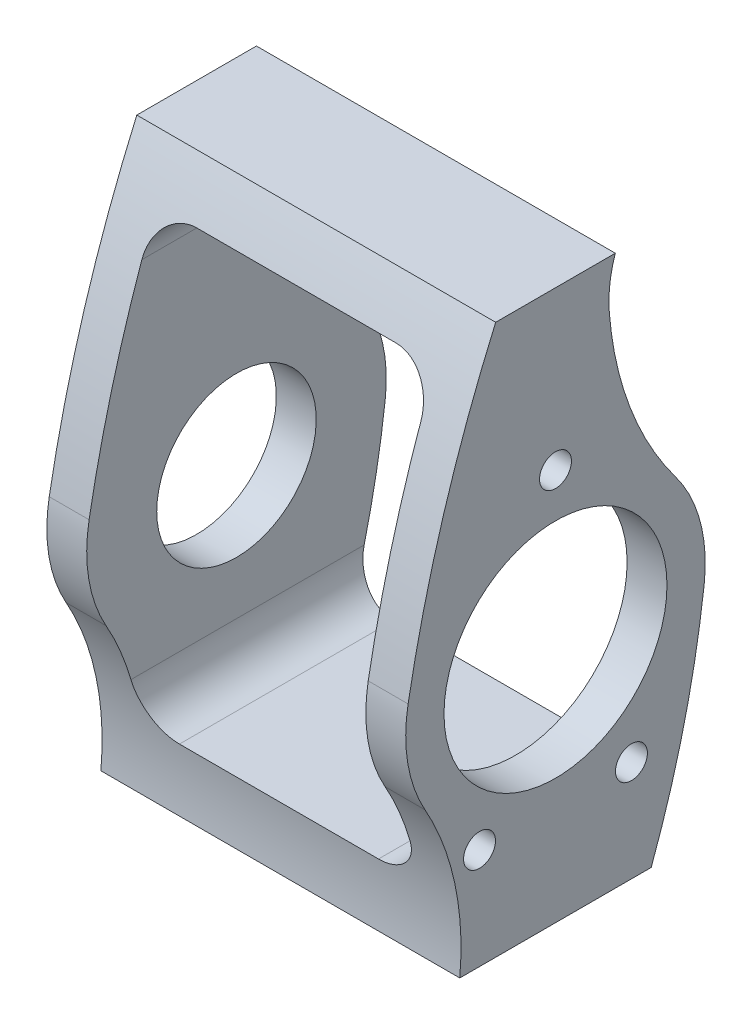
SolidWorks part; units mm, degrees
material "AISI 4340 Steel, normalized"
ref_plane "Front Plane" through (0, 0, 0) normal (0, 0, 1) x (1, 0, 0)
ref_plane "Top Plane" through (0, 0, 0) normal (0, 1, 0) x (1, 0, 0)
ref_plane "Right Plane" through (0, 0, 0) normal (1, 0, 0) x (0, 0, -1)
other "Center of Mass"
sketch "Sketch1" plane through (0, 0, 0) normal (1, 0, 0) x (0, 0, -1)
  line L0 (9.525, 49.899) -> (-9.525, 49.899)
  line L1 (9.525, 49.899) -> (-7.4687, 0) construction
  line L2 (0, 0) -> (9.525, 49.899) construction
  line L3 (-15.24, -37.6743) -> (15.24, -37.6743)
  line L4 (-15.24, -37.6743) -> (0, 0) construction
  line L5 (0, 0) -> (0, -50.8) construction
  line L6 (-7.3617, -24.2335) -> (-7.431, -18.808) construction
  line L7 (-7.431, -18.808) -> (-12.1642, -16.1553) construction
  line L8 (-12.1642, -16.1553) -> (-16.8282, -18.928) construction
  line L9 (-16.8282, -18.928) -> (-16.7589, -24.3535) construction
  line L10 (-16.7589, -24.3535) -> (-12.0257, -27.0063) construction
  line L11 (-12.0257, -27.0063) -> (-7.3617, -24.2335) construction
  line L12 (16.7589, -24.3535) -> (16.8282, -18.928) construction
  line L13 (16.8282, -18.928) -> (12.1642, -16.1553) construction
  line L14 (12.1642, -16.1553) -> (7.431, -18.808) construction
  line L15 (7.431, -18.808) -> (7.3617, -24.2335) construction
  line L16 (7.3617, -24.2335) -> (12.0257, -27.0063) construction
  line L17 (12.0257, -27.0063) -> (16.7589, -24.3535) construction
  line L18 (2.713, 20.04) -> (5.4259, 24.739) construction
  line L19 (5.4259, 24.739) -> (2.713, 29.438) construction
  line L20 (2.713, 29.438) -> (-2.713, 29.438) construction
  line L21 (-2.713, 29.438) -> (-5.4259, 24.739) construction
  line L22 (-5.4259, 24.739) -> (-2.713, 20.04) construction
  line L23 (-2.713, 20.04) -> (2.713, 20.04) construction
  line L24 (-15.4577, -27.5143) -> (18.4762, -27.5143) construction
  line L25 (15.24, -37.6743) -> (15.24, -27.5143) construction
  line L26 (12.0949, -21.5808) -> (-12.0949, -21.5808) construction
  circle A0 centre (0, 0) radius 17.5 construction
  circle A1 centre (0, 0) radius 20.04 construction
  circle A2 centre (0, 0) radius 50.8 construction
  circle A3 centre (0, 0) radius 40.64 construction
  circle A4 centre (0, 0) radius 23.85 construction
  circle A7 centre (-12.0949, -21.5808) radius 4.699 construction
  circle A8 centre (12.0949, -21.5808) radius 4.699 construction
  circle A9 centre (0, 24.739) radius 4.699 construction
  arc A12 (9.525, 49.899) -> (8.5654, 42.279) centre (27.5579, 43.7577) ccw
  arc A13 (19.0999, 14.2834) -> (8.5654, 42.279) centre (62.1106, 46.4478) cw
  arc A14 (-15.24, -37.6743) -> (-20.7762, -11.7121) centre (-59.4974, -33.5404) ccw
  arc A15 (-20.7762, -11.7121) -> (-23.4703, 4.2386) centre (0, 0) cw
  arc A16 (23.6786, -2.8538) -> (19.0999, 14.2834) centre (0, 0) ccw
  arc A18 (-9.525, 49.899) -> (-23.4703, 4.2386) centre (176.495, -31.8738) ccw
  arc A19 (15.24, -37.6743) -> (23.6786, -2.8538) centre (-127.6264, 15.3818) ccw
  point P37 (9.7976, -17.4817)
  point P38 (-9.7976, -17.4817)
  point P39 (0, 20.04)
  point P56 (0, -21.5808)
  dimension "D1" = 35
  dimension "D3" = 101.6
  dimension "D13" = 19.05
  dimension "D15" = 44.45
  dimension "D16" = 152.4
  dimension "D17" = 203.2
  dimension "D2" = 2.54
  dimension "D4" = 10.16
  dimension "D5" = 8
  dimension "D7" = 6.35
  dimension "D8" = 9.398
  dimension "D6" = 19.05
  dimension "D9" = 90
  dimension "D10" = 10.16
  dimension "D11" = 0.508
  dimension "D12" = 30.48
  dimension "D14" = 7.62
extrude "Boss-Extrude1" add sketch "Sketch1" along normal blind 57.15
sketch "Sketch2" plane through (0, 0, 0) normal (0, 0, 1) x (1, 0, 0)
  line L0 (57.15, 49.899) -> (0, 49.899) construction
  line L1 (6.35, 42.279) -> (50.8, 42.279)
  line L2 (6.35, 42.279) -> (6.35, -27.5143)
  line L3 (6.35, -27.5143) -> (50.8, -27.5143)
  line L4 (50.8, 42.279) -> (50.8, -27.5143)
  line L5 (57.15, -37.6743) -> (0, -37.6743) construction
  line L6 (0, 49.899) -> (0, 4.2386) construction
  line L7 (57.15, 4.2386) -> (57.15, 49.899) construction
  dimension "D1" = 7.62
  dimension "D2" = 10.16
  dimension "D3" = 6.35
  dimension "D4" = 6.35
extrude "Cut-Extrude1" cut sketch "Sketch2" against normal through all both and the other way through all
fillet "Fillet1" radius 6.3754 4 edges at (6.35, -27.5143, -1.5772) (6.35, 42.279, 2.0631) (50.8, 42.279, 2.0631) (50.8, -27.5143, -1.5772)
sketch "Sketch3" plane through (57.15, 0, 0) normal (1, 0, 0) x (0, 0, -1)
  circle A0 centre (0, 0) radius 17.754
  dimension "D1" = 35.508
extrude "Cut-Extrude2" cut sketch "Sketch3" against normal up to surface (6.35 mm away) up to face at (50.8, 4.1733, 0.5753)
sketch "Sketch4" plane through (57.15, 0, 0) normal (1, 0, 0) x (0, 0, -1)
  circle A0 centre (0, 24.739) radius 2.54
  circle A1 centre (-12.0949, -21.5808) radius 2.54
  circle A2 centre (12.0949, -21.5808) radius 2.54
  point P0 (-12.0949, -21.5808)
  point P2 (12.0949, -21.5808)
  point P4 (0, 24.739)
  dimension "D1" = 5.08
extrude "Cut-Extrude3" cut sketch "Sketch4" against normal up to next
sketch "Sketch5" plane through (0, 0, 0) normal (-1, 0, 0) x (0, 0, 1)
  circle A0 centre (0, 0) radius 12.7
  dimension "D1" = 25.4
extrude "Cut-Extrude4" cut sketch "Sketch5" against normal up to next
equation "\"D1@Sketch1\"=35mm"
equation "\"D1@Sketch3\"=35mm+0.02in"
